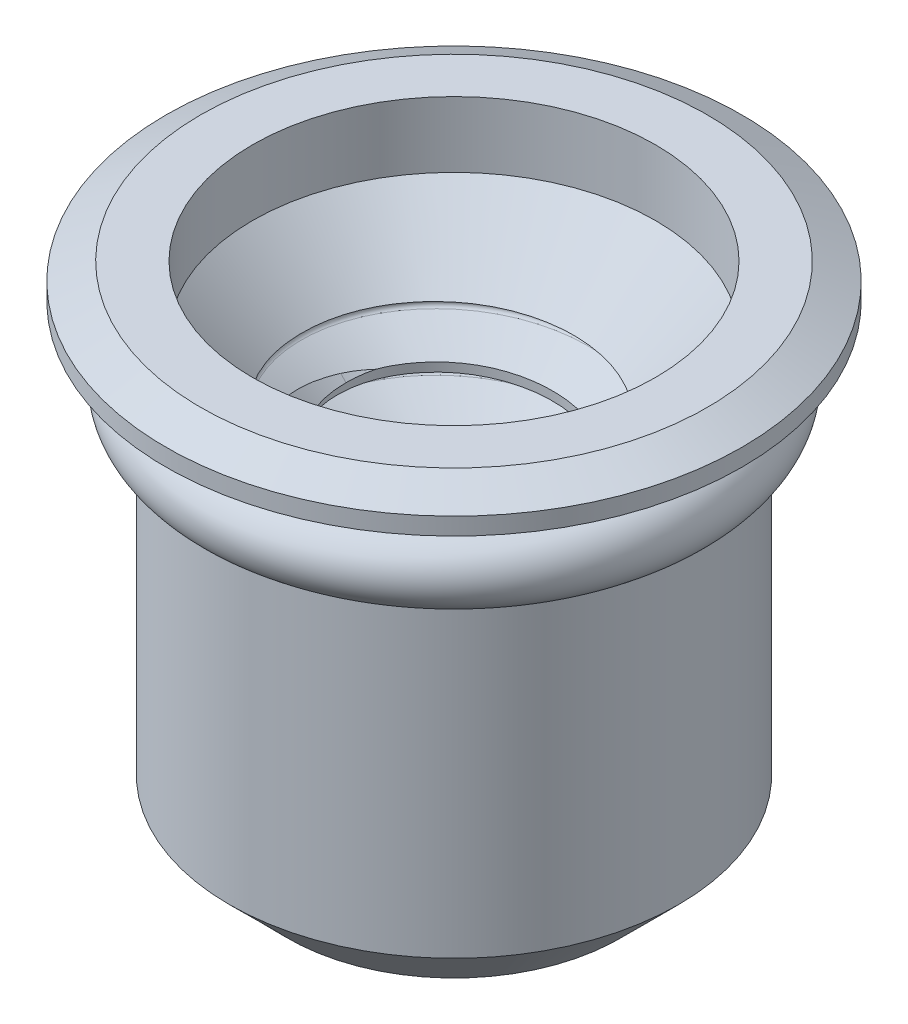
SolidWorks part; units mm, degrees
material "Plain Carbon Steel"
ref_plane "Front Plane" through (0, 0, 0) normal (0, 0, 1) x (1, 0, 0)
ref_plane "Top Plane" through (0, 0, 0) normal (0, 1, 0) x (1, 0, 0)
ref_plane "Right Plane" through (0, 0, 0) normal (1, 0, 0) x (0, 0, -1)
sketch "Sketch1" plane through (0, 0, 0) normal (0, 0, 1) x (1, 0, 0)
  line L0 (-4.953, -14.2081) -> (-3.6671, -15.494)
  line L1 (-4.445, -5.842) -> (-2.3813, -5.842) construction
  line L2 (-2.3813, -5.842) -> (-2.3813, -7.9057) construction
  line L3 (-3.6671, -15.494) -> (-3.175, -15.494)
  line L4 (6.35, 0) -> (5.588, 0) construction
  line L5 (-3.175, -15.494) -> (-2.3812, -14.7002)
  line L6 (6.35, -0.381) -> (6.35, 0) construction
  line L7 (-2.3812, -14.7002) -> (-2.3813, -7.9057)
  line L8 (4.953, -15.494) -> (3.6671, -15.494) construction
  line L9 (-2.3813, -7.9057) -> (-4.445, -5.842)
  line L10 (2.3812, -15.494) -> (2.3812, -14.7002) construction
  line L11 (-4.445, -5.842) -> (-4.445, 0)
  line L12 (4.953, -14.2081) -> (4.953, -15.494) construction
  line L13 (3.175, -15.494) -> (2.3812, -15.494) construction
  line L14 (-4.445, 0) -> (-5.588, 0)
  line L15 (-5.588, 0) -> (-6.35, -0.381)
  line L16 (6.35, -11.0998) -> (6.35, -1.4478) construction
  line L17 (-6.35, -0.381) -> (-6.35, -0.762)
  line L18 (6.35, -0.762) -> (4.953, -0.762) construction
  line L19 (-6.35, -0.762) -> (-4.953, -0.762)
  line L20 (-4.953, -0.762) -> (-4.953, -14.2081)
  line L21 (0, 0) -> (0, -15.494) construction
  line L22 (-6.35, -0.762) -> (-6.35, 0) construction
  line L23 (-6.35, 0) -> (-5.588, 0) construction
  line L24 (-4.953, -14.2081) -> (-4.953, -15.494) construction
  line L25 (-4.953, -15.494) -> (-3.6671, -15.494) construction
  line L26 (-3.175, -15.494) -> (-2.3812, -15.494) construction
  line L27 (-2.3812, -15.494) -> (-2.3812, -14.7002) construction
  line L28 (-2.3812, -15.494) -> (0, -15.494) construction
  line L29 (6.35, -0.381) -> (6.35, -0.762) construction
  line L30 (-3.6671, -15.494) -> (-2.3812, -15.494) construction
  line L32 (0, 0) -> (-4.445, 0) construction
  dimension "D7" = 4.7625
  dimension "D8" = 45
  dimension "D12" = 9.652
  dimension "D2" = 8.89
revolve "Revolve1" add sketch "Sketch1" angle 360 about L21
sketch "Sketch3" plane through (0, -15.494, 0) normal (0, -1, 0) x (1, 0, 0)
  circle A1 centre (0, 0) radius 3.175
  point P1 (3.175, 0)
  dimension "D1" = 6.35
ref_plane "Plane1" through (-4.953, 0, 0) normal (1, 0, 0) x (0, 0, -1)
sketch "Sketch2" plane through (-4.953, 0, 0) normal (1, 0, 0) x (0, 0, -1)
  line L0 (-4.953, -0.762) -> (4.953, -0.762) construction
  line L1 (-0.127, -0.762) -> (0.127, -0.762)
  line L2 (-0.127, -0.762) -> (-0.127, -5.334)
  line L3 (-0.127, -5.334) -> (0.127, -5.334) construction
  line L4 (0.127, -0.762) -> (0.127, -5.334)
  line L5 (0, -0.762) -> (0, 0) construction
  line L6 (-0.127, -5.334) -> (0, -5.842)
  line L7 (0, -5.842) -> (0.127, -5.334)
  line L8 (0, -5.334) -> (0, -5.842) construction
  line L10 (0, -0.762) -> (0, -5.334) construction
  line L11 (0, -5.588) -> (0, -5.334) construction
  dimension "D1" = 0.254
extrude "Extrude1" cut sketch "Sketch2" along normal through all draft 45
ref_axis "Axis1" through (0, 0, 0) along (0, -1, 0)
pattern_circular "CirPattern1" count 54 over 360 about axis through (0, 0, 0) along (0, -1, 0) of "Extrude1"
curve "Helix/Spiral1" pitch 1.27 height 23.9816 radius 3.175 centre (0, -15.494, 0) axis (0, 1, 0) start towards (1, 0, 0) parameters "Height"=23.9816, "Pitch"=1.27
sketch "Sketch4" plane through (0, 0, 0) normal (0, 0, 1) x (1, 0, 0)
  line L0 (2.2126, -14.9384) -> (2.2126, -16.2084) construction
  line L1 (2.2126, -16.2084) -> (3.3125, -15.5734) construction
  line L2 (2.2126, -14.9384) -> (3.3125, -15.5734) construction
  line L3 (2.3501, -15.0178) -> (2.3501, -16.129) construction
  line L6 (2.2126, -15.5734) -> (2.3501, -15.5734) construction
  line L8 (3.175, -15.5734) -> (3.3125, -15.5734) construction
  line L9 (3.175, -15.494) -> (3.175, -15.6527) construction
  line L11 (2.2814, -14.9781) -> (2.2814, -16.1687)
  line L12 (2.2814, -16.1687) -> (3.175, -15.6527)
  line L14 (3.175, -15.494) -> (2.2814, -14.9781)
  arc A0 (3.175, -15.6527) -> (3.175, -15.494) centre (3.1292, -15.5734) ccw
  point P13 (2.2814, -15.5734)
  dimension "D1" = 1.27
  dimension "D2" = 0.1588
sweep "Cut-Sweep1" cut profiles "Sketch4" path "Helix/Spiral1" align with end faces yes
ref_plane "Plane2" through (0, -1.4478, 0) normal (0, -1, 0) x (1, 0, 0)
sketch "Sketch5" plane through (0, -1.4478, 0) normal (0, -1, 0) x (1, 0, 0)
  circle A0 centre (0, 0) radius 4.953
  point P3 (-4.953, 0)
extrude "Extrude2" cut sketch "Sketch5" along normal blind 4.3942
pattern_linear "LPattern1" count 2 spacing 4.3942 along (0, 1, 0) of bodies 117
delete or keep bodies "Body-Delete1" type delete bodies bodies 117
combine bodies "Combine1" operation type add bodies to combine 118 119
sketch "Sketch6" plane through (0, 0, 0) normal (0, 0, 1) x (1, 0, 0)
  line L0 (-4.953, -1.4478) -> (-4.445, -1.4478)
  line L1 (-4.445, -1.4478) -> (-4.445, -2.9718)
  line L2 (-4.445, -2.9718) -> (-4.953, -2.9718)
  line L3 (-4.445, -5.842) -> (-4.445, 0) construction
  line L4 (-6.985, -1.4478) -> (6.985, -1.4478) construction
  line L5 (-4.953, -0.762) -> (-4.953, -14.2081) construction
  line L6 (0, 0) -> (0, -15.494) construction
  line L7 (0, 0) -> (0, -15.494) construction
  arc A0 (-4.953, -1.4478) -> (-4.953, -2.9718) centre (-4.953, -2.2098) ccw
  dimension "D1" = 1.524
revolve "Revolve2" add sketch "Sketch6" angle 360 about L7
equation "\"Height@Helix/Spiral1\" = \"Body Lg@Sketch1\" + \"Pitch@Helix/Spiral1\" +  (  pi  / 10 ) "
equation "\"D1@Sketch4\" = \"Pitch@Helix/Spiral1\""
equation "\"D2@Sketch4\" = \"D1@Sketch4\" / 8"
equation "\"D1@Extrude2\" = \"D1@Sketch1\""
equation "\"D3@LPattern1\" = \"D1@Extrude2\""
equation "\"D7@Sketch1\" = \"Thread Dia@Sketch1\" -  ( \"Pitch@Helix/Spiral1\" )  * 1.25"
equation "\"D2@Sketch1\" =  \"Thread Dia@Sketch1\" + ( \"Pitch@Helix/Spiral1\" ) * 2"
equation "\"D12@Sketch1\" = \"Max Installed Lg@Sketch1\""
equation "\"D1@Sketch3\" = \"Thread Dia@Sketch1\""
